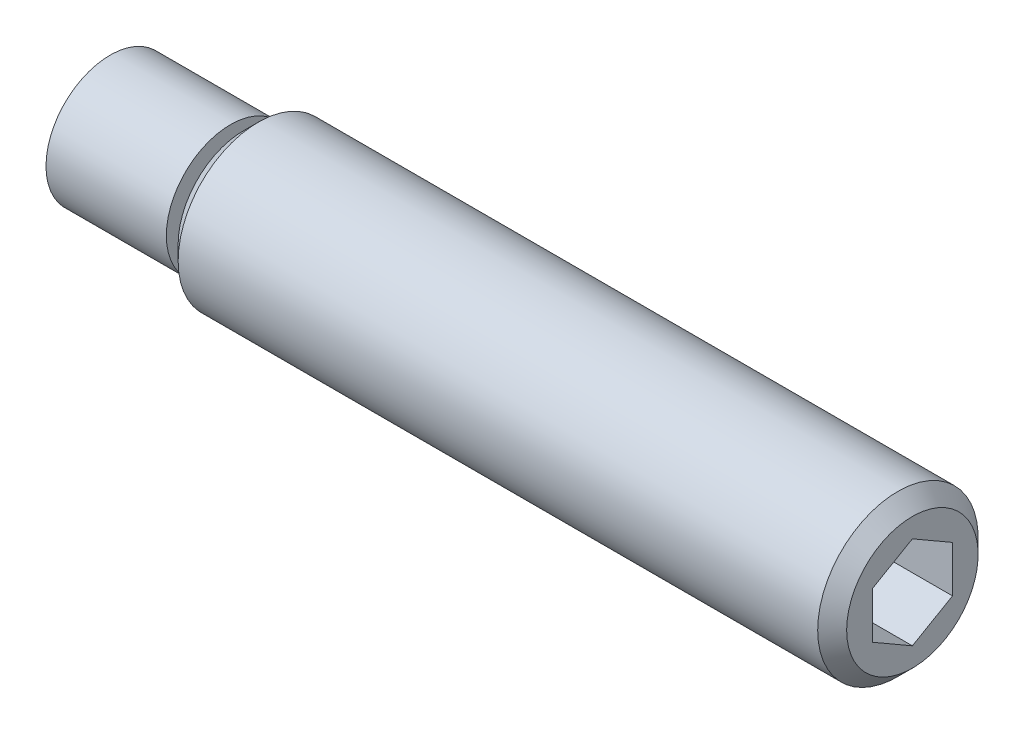
SolidWorks part; units mm, degrees
ref_plane "前视基准面" through (0, 0, 0) normal (0, 0, 1) x (1, 0, 0)
ref_plane "上视基准面" through (0, 0, 0) normal (0, 1, 0) x (1, 0, 0)
ref_plane "右视基准面" through (0, 0, 0) normal (1, 0, 0) x (0, 0, -1)
sketch "草图1" plane through (0, 0, 0) normal (0, 0, 1) x (1, 0, 0)
  line L0 (-5, 0) -> (-5, 2.4)
  line L1 (-5, 2.4) -> (-0.5, 2.4)
  line L2 (-0.5, 2.4) -> (-0.5, 1.5)
  line L3 (-0.5, 1.5) -> (0, 1.5)
  line L4 (0, 1.5) -> (0, 2.4585)
  line L5 (0, 2.4585) -> (0.5415, 3)
  line L6 (0.5415, 3) -> (24.4585, 3)
  line L7 (24.4585, 3) -> (25, 2.4585)
  line L8 (25, 2.4585) -> (25, 0)
  line L9 (25, 0) -> (-5, 0)
  line L10 (25, 0) -> (-5, 0) construction
revolve "旋转1" add sketch "草图1" angle 360 about L10 reverse direction yes
cosmetic thread "装饰螺纹线1" parameters "D1"=25, "D2"=4.917
ref_plane "基准面1" through (25, 0, 0) normal (1, 0, 0) x (0, 0, -1)
sketch "草图2" plane through (0, 0, 0) normal (0, 1, 0) x (1, 0, 0)
  line L0 (21.134, 0) -> (22, 1.5)
  line L1 (22, 1.5) -> (25, 1.5)
  line L2 (25, 1.5) -> (25, 0)
  line L3 (25, 0) -> (21.134, 0)
  line L4 (25, 0) -> (21.134, 0) construction
revolve "切除-旋转1" cut sketch "草图2" angle 360 about L4 reverse direction yes
sketch "草图3" plane through (25, 0, 0) normal (1, 0, 0) x (0, 0, -1)
  line L0 (-1.5, 0.866) -> (-1.5, -0.866)
  line L1 (-1.5, -0.866) -> (0, -1.7321)
  line L2 (0, -1.7321) -> (1.5, -0.866)
  line L3 (1.5, -0.866) -> (1.5, 0.866)
  line L4 (1.5, 0.866) -> (0, 1.7321)
  line L5 (0, 1.7321) -> (-1.5, 0.866)
extrude "切除-拉伸1" cut sketch "草图3" against normal blind 3
ref_plane "基准面2" through (12.5, 0, 0) normal (1, 0, 0) x (0, 0, -1)
ref_plane "ussb_n XY" through (12.5, 0, 0) normal (1, 0, 0) x (0, 0, -1)
ref_plane "ussb_n XZ" through (0, 0, 0) normal (0, -1, 0) x (1, 0, 0)
ref_plane "ussb_n YZ" through (0, 0, 0) normal (0, 0, -1) x (-1, 0, 0)
ref_axis "ussb_n X" through (12.5, 0, 80.9) along (0, 0, -1)
ref_axis "ussb_n Y" through (12.5, -50, 0) along (0, 1, 0)
ref_axis "ussb_n Z" through (80.9, 0, 0) along (-1, 0, 0)
sketch3d "ussb_n"
  point P0 (12.5, 0, 0)
